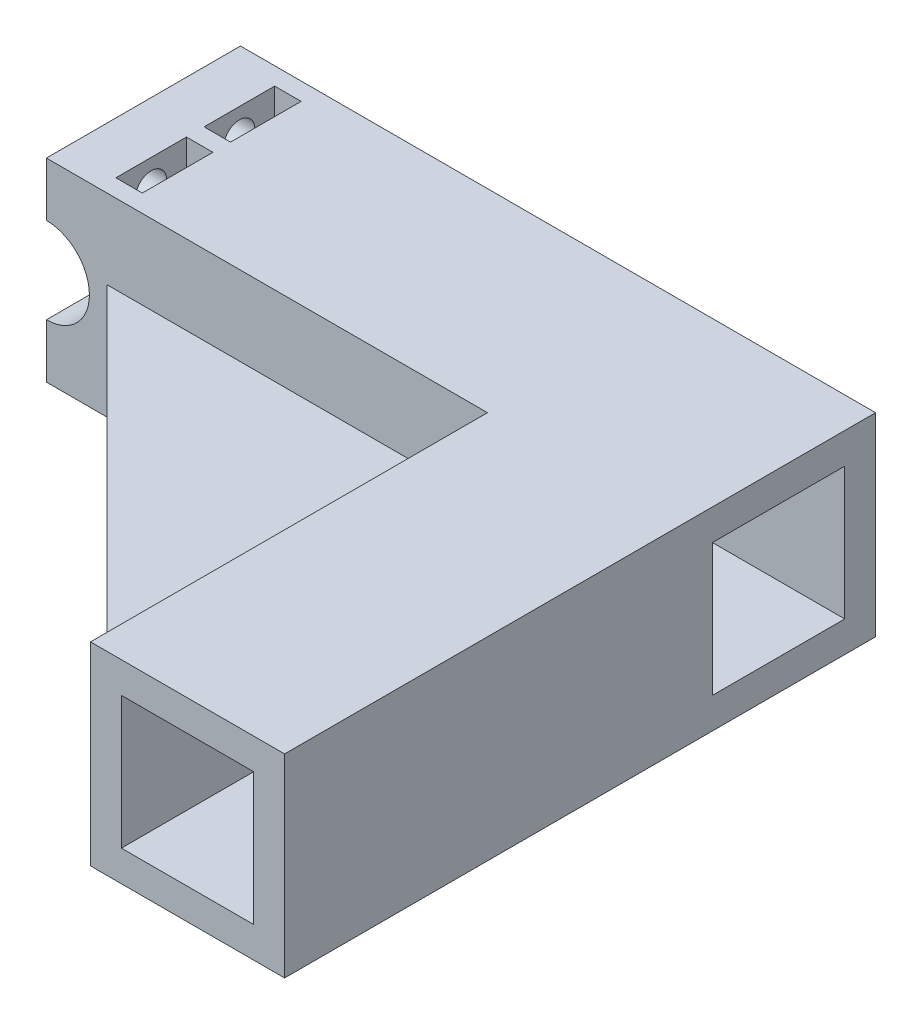
SolidWorks part; units mm, degrees
ref_plane "Front Plane" through (0, 0, 0) normal (0, 0, 1) x (1, 0, 0)
ref_plane "Top Plane" through (0, 0, 0) normal (0, 1, 0) x (1, 0, 0)
ref_plane "Right Plane" through (0, 0, 0) normal (1, 0, 0) x (0, 0, -1)
sketch "Sketch1" plane through (0, 0, 0) normal (0, 0, 1) x (1, 0, 0)
  line L0 (42.1382, 7.6443) -> (42.1382, -14.3557) construction
  line L1 (-7.8618, 7.6443) -> (64.1382, 7.6443)
  line L2 (-7.8618, 7.6443) -> (-7.8618, 1.5193)
  line L3 (-7.8618, -14.3557) -> (64.1382, -14.3557)
  line L4 (64.1382, 7.6443) -> (64.1382, -14.3557)
  line L5 (-7.8618, -8.2307) -> (-7.8618, -14.3557)
  arc A0 (-7.8618, -8.2307) -> (-7.8618, 1.5193) centre (-7.8618, -3.3557) ccw
  dimension "D4" = 9.75
  dimension "D1" = 22
  dimension "D2" = 50
  dimension "D3" = 22
extrude "Boss-Extrude1" add sketch "Sketch1" along normal blind 22
sketch "Sketch2" plane through (0, 0, 22) normal (0, 0, 1) x (1, 0, 0)
  line L0 (-7.8618, -14.3557) -> (64.1382, -14.3557) construction
  line L1 (64.1382, 7.6443) -> (42.1382, 7.6443)
  line L2 (64.1382, 7.6443) -> (64.1382, -14.3557)
  line L3 (64.1382, -14.3557) -> (42.1382, -14.3557)
  line L4 (42.1382, 7.6443) -> (42.1382, -14.3557)
  dimension "D1" = 22
extrude "Boss-Extrude2" add sketch "Sketch2" along normal blind 45
sketch "Sketch3" plane through (0, 0, 67) normal (0, 0, 1) x (1, 0, 0)
  line L0 (64.1382, -14.3557) -> (64.1382, 7.6443) construction
  line L1 (45.6382, 4.1443) -> (60.6382, 4.1443)
  line L2 (45.6382, 4.1443) -> (45.6382, -10.8557)
  line L3 (45.6382, -10.8557) -> (60.6382, -10.8557)
  line L4 (60.6382, 4.1443) -> (60.6382, -10.8557)
  line L5 (64.1382, 7.6443) -> (42.1382, 7.6443) construction
  dimension "D1" = 15
  dimension "D2" = 3.5
  dimension "D3" = 15
  dimension "D4" = 3.5
extrude "Cut-Extrude1" cut sketch "Sketch3" against normal offset from surface (43 mm away) 2 up to face at (9.6173, -1.5223, 22)
sketch "Sketch4" plane through (64.1382, 0, 0) normal (1, 0, 0) x (0, 0, -1)
  line L0 (-67, 7.6443) -> (0, 7.6443) construction
  line L1 (-3.5, 4.1443) -> (-18.5, 4.1443)
  line L2 (-3.5, 4.1443) -> (-3.5, -10.8557)
  line L3 (-3.5, -10.8557) -> (-18.5, -10.8557)
  line L4 (-18.5, 4.1443) -> (-18.5, -10.8557)
  line L5 (0, -14.3557) -> (0, 7.6443) construction
  dimension "D1" = 15
  dimension "D2" = 15
  dimension "D3" = 3.5
  dimension "D4" = 3.5
extrude "Cut-Extrude2" cut sketch "Sketch4" against normal blind 45
sketch "Sketch5" plane through (-7.8618, 0, 0) normal (-1, 0, 0) x (0, 0, 1)
  line L0 (0, 4.5818) -> (22, 4.5818) construction
  line L1 (0, 7.6443) -> (0, 1.5193) construction
  line L2 (22, 7.6443) -> (22, 1.5193) construction
  line L3 (0, -11.2932) -> (22, -11.2932) construction
  line L4 (0, -8.2307) -> (0, -14.3557) construction
  line L5 (22, -8.2307) -> (22, -14.3557) construction
  circle A0 centre (6, 4.5818) radius 1.75
  circle A1 centre (16, 4.5818) radius 1.75
  circle A2 centre (6, -11.2932) radius 1.75
  circle A3 centre (16, -11.2932) radius 1.75
  dimension "D1" = 3.5
  dimension "D2" = 10
  dimension "D3" = 10
  dimension "D4" = 6
  dimension "D5" = 6
extrude "Cut-Extrude3" cut sketch "Sketch5" against normal offset from surface (25 mm away) 2 up to face at (19.1382, -3.3557, 11)
ref_plane "Plane1" through (0, -3.3557, 0) normal (0, 1, 0) x (1, 0, 0)
sketch "Sketch6" plane through (0, -3.3557, 0) normal (0, 1, 0) x (1, 0, 0)
  line L0 (-0.9868, -22) -> (42.1382, -65.125)
  line L1 (42.1382, -22) -> (-7.8618, -22) construction
  line L2 (42.1382, -67) -> (42.1382, -22) construction
  line L3 (42.1382, -65.125) -> (42.1382, -22)
  line L4 (42.1382, -22) -> (-0.9868, -22)
  line L5 (-2.9868, -22) -> (-2.9868, 0) construction
  dimension "D1" = 2
  dimension "D2" = 45
extrude "Boss-Extrude3" add sketch "Sketch6" along normal blind 2 and the other way blind 2
sketch "Sketch7" plane through (0, 7.6443, 0) normal (0, 1, 0) x (1, 0, 0)
  line L0 (-2.9868, -22) -> (-2.9868, 0) construction
  line L1 (-1.9868, -12) -> (1.0132, -12)
  line L2 (-1.9868, -12) -> (-1.9868, -20)
  line L3 (-1.9868, -20) -> (1.0132, -20)
  line L4 (1.0132, -12) -> (1.0132, -20)
  line L5 (-1.9868, -2) -> (1.0132, -2)
  line L6 (-1.9868, -2) -> (-1.9868, -10)
  line L7 (-1.9868, -10) -> (1.0132, -10)
  line L8 (1.0132, -2) -> (1.0132, -10)
  line L9 (42.1382, -22) -> (-7.8618, -22) construction
  dimension "D1" = 3
  dimension "D2" = 3
  dimension "D3" = 1
  dimension "D4" = 2
  dimension "D5" = 2
  dimension "D6" = 2
extrude "Cut-Extrude4" cut sketch "Sketch7" against normal blind 7
